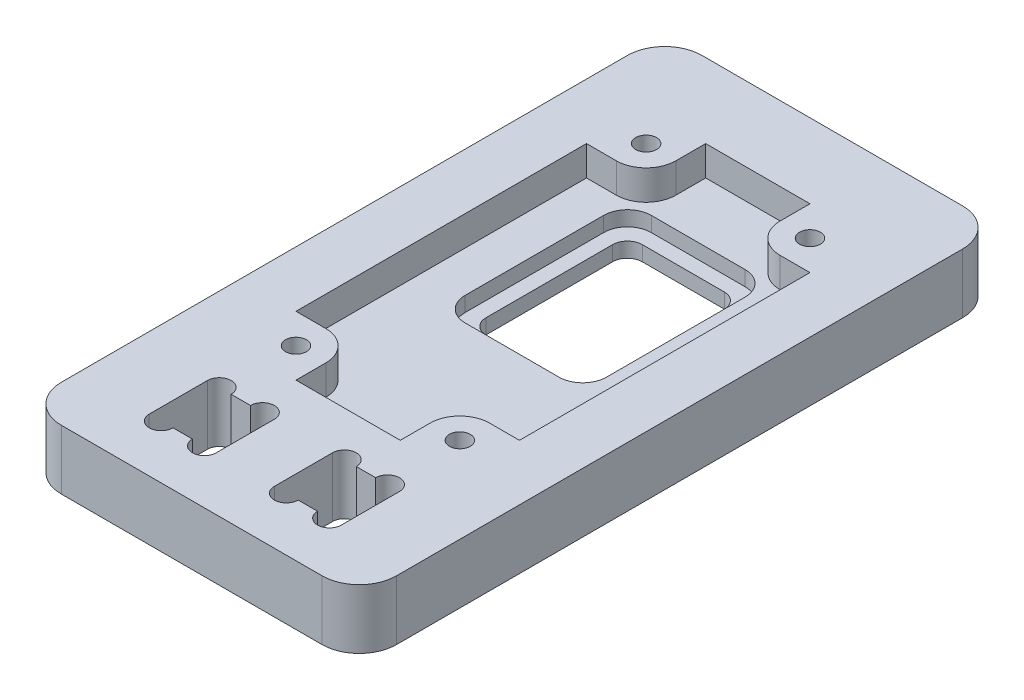
SolidWorks part; units mm, degrees
ref_plane "Front Plane" through (0, 0, 0) normal (0, 0, 1) x (1, 0, 0)
ref_plane "Top Plane" through (0, 0, 0) normal (0, 1, 0) x (1, 0, 0)
ref_plane "Right Plane" through (0, 0, 0) normal (1, 0, 0) x (0, 0, -1)
sketch "Sketch1" plane through (0, 0, 0) normal (0, 1, 0) x (1, 0, 0)
  line L0 (7.5, 21) -> (7.5, 41) construction
  line L1 (2, 0) -> (13, 0)
  line L2 (0, 2) -> (0, 19)
  line L3 (2, 21) -> (13, 21)
  line L4 (15, 2) -> (15, 19)
  line L5 (3.6, -30) -> (11.4, -30) construction
  line L6 (-10, 41) -> (25, 41)
  line L7 (-15, 36) -> (-15, -40)
  line L8 (-10, -45) -> (25, -45)
  line L9 (30, 36) -> (30, -40)
  line L10 (-5.4, -30) -> (3.6, -30)
  line L11 (-5.4, -30) -> (-5.4, -37.8)
  line L12 (-5.4, -37.8) -> (3.6, -37.8)
  line L13 (3.6, -30) -> (3.6, -37.8)
  line L14 (11.4, -30) -> (20.4, -30)
  line L15 (11.4, -30) -> (11.4, -37.8)
  line L16 (11.4, -37.8) -> (20.4, -37.8)
  line L17 (20.4, -30) -> (20.4, -37.8)
  line L18 (7.5, 0) -> (7.5, -45) construction
  arc A0 (13, 0) -> (15, 2) centre (13, 2) ccw
  arc A1 (2, 0) -> (0, 2) centre (2, 2) cw
  arc A2 (15, 19) -> (13, 21) centre (13, 19) ccw
  arc A3 (0, 19) -> (2, 21) centre (2, 19) cw
  arc A4 (30, 36) -> (25, 41) centre (25, 36) ccw
  arc A5 (25, -45) -> (30, -40) centre (25, -40) ccw
  arc A6 (-10, -45) -> (-15, -40) centre (-10, -40) cw
  arc A7 (-15, 36) -> (-10, 41) centre (-10, 36) cw
  circle A8 centre (-3.8, -30) radius 1.6
  circle A9 centre (2, -30) radius 1.6
  circle A10 centre (-3.8, -37.8) radius 1.6
  circle A11 centre (2, -37.8) radius 1.6
  circle A12 centre (13, -30) radius 1.6
  circle A13 centre (18.8, -30) radius 1.6
  circle A14 centre (13, -37.8) radius 1.6
  circle A15 centre (18.8, -37.8) radius 1.6
  point P9 (0, 0)
  point P12 (15, 21)
  point P15 (0, 21)
  point P22 (7.5, 41)
  point P41 (7.5, -30)
  dimension "D3" = 2
  dimension "D6" = 5
  dimension "D14" = 3.2
  dimension "D15" = 3.2
  dimension "D16" = 3.2
  dimension "D17" = 3.2
  dimension "D18" = 3.2
  dimension "D19" = 3.2
  dimension "D20" = 3.2
  dimension "D21" = 3.2
  dimension "D1" = 21
  dimension "D2" = 15
  dimension "D4" = 20
  dimension "D5" = 45
  dimension "D7" = 35
  dimension "D8" = 7.8
  dimension "D9" = 7.8
  dimension "D10" = 15
  dimension "D11" = 9
  dimension "D12" = 9
  dimension "D13" = 7.8
extrude "Boss-Extrude1" add sketch "Sketch1" along normal blind 8 contours A7 L7 A6 L8 A5 L9 A4 L6 A15 L16 A14 L15 A12 L14 A13 L17 A11 L12 A10 L11 A8 L10 A9 L13 L2 A3 L3 A2 L4 A0 L1 A1 region at (7.5, 0, 1.5213)
sketch "Sketch3" plane through (0, 8, 0) normal (0, 1, 0) x (1, 0, 0)
  line L0 (7.5, 31) -> (7.5, 21) construction
  line L1 (-7.5, 31) -> (22.5, 31)
  line L2 (-7.5, 31) -> (-7.5, -24)
  line L3 (-7.5, -24) -> (22.5, -24)
  line L4 (22.5, 31) -> (22.5, -24)
  line L5 (2, 21) -> (13, 21) construction
  line L6 (0.5, 27) -> (0.5, 31)
  line L7 (-3.5, 23) -> (-7.5, 23)
  line L8 (14.5, 27) -> (14.5, 31)
  line L9 (18.5, 23) -> (22.5, 23)
  line L10 (0.5, -20) -> (0.5, -24)
  line L11 (14.5, -20) -> (14.5, -24)
  line L12 (18.5, -16) -> (22.5, -16)
  line L13 (-3.5, -16) -> (-7.5, -16)
  circle A0 centre (-3.5, 27) radius 4
  circle A1 centre (18.5, 27) radius 4
  circle A2 centre (-3.5, -20) radius 4
  circle A3 centre (18.5, -20) radius 4
  circle A4 centre (-3.5, 27) radius 1.4
  circle A5 centre (18.5, 27) radius 1.4
  circle A6 centre (-3.5, -20) radius 1.4
  circle A7 centre (18.5, -20) radius 1.4
  line M34 (0, 2) -> (0, 19)
  arc M35 (0, 19) -> (2, 21) centre (2, 19) cw
  line M36 (2, 21) -> (13, 21)
  arc M37 (13, 21) -> (15, 19) centre (13, 19) cw
  line M38 (15, 19) -> (15, 2)
  arc M39 (15, 2) -> (13, 0) centre (13, 2) cw
  line M40 (13, 0) -> (2, 0)
  arc M41 (2, 0) -> (0, 2) centre (2, 2) cw
  dimension "D4" = 8
  dimension "D5" = 8
  dimension "D6" = 8
  dimension "D7" = 8
  dimension "D8" = 2.8
  dimension "D9" = 2.8
  dimension "D10" = 2.8
  dimension "D11" = 2.8
  dimension "D1" = 55
  dimension "D2" = 30
  dimension "D3" = 10
extrude "Cut-Extrude1" cut sketch "Sketch3" against normal blind 4 contours A3 L12 L4 L9 A1 L8 L1 L6 A0 L7 L2 L13 A2 L10 L3 L11 M36 M37 M38 M39 M40 M41 M34 M35 | A4 | A5 | A6 | A7 region at (7.5, 8, -30.3735)
sketch "Sketch5" plane through (0, 4, 0) normal (0, 1, 0) x (1, 0, 0)
  line L0 (7.5, 0) -> (7.5, -2) construction
  line L1 (1.2, -2) -> (13.8, -2)
  line L2 (-2, 1.2) -> (-2, 19.8)
  line L3 (1.2, 23) -> (13.8, 23)
  line L4 (17, 1.2) -> (17, 19.8)
  line L5 (13, 0) -> (2, 0) construction
  line L7 (2, 21) -> (13, 21) construction
  line L8 (0, 2) -> (0, 19) construction
  line L10 (0, 10.5) -> (-2, 10.5) construction
  arc A0 (-2, 1.2) -> (1.2, -2) centre (1.2, 1.2) ccw
  arc A1 (17, 19.8) -> (13.8, 23) centre (13.8, 19.8) ccw
  arc A2 (-2, 19.8) -> (1.2, 23) centre (1.2, 19.8) cw
  arc A3 (13.8, -2) -> (17, 1.2) centre (13.8, 1.2) ccw
  dimension "D1" = 3.2
  dimension "D4" = 3.2
  dimension "D5" = 3.2
  dimension "D2" = 2
  dimension "D3" = 2
extrude "Cut-Extrude2" cut sketch "Sketch5" against normal blind 2
